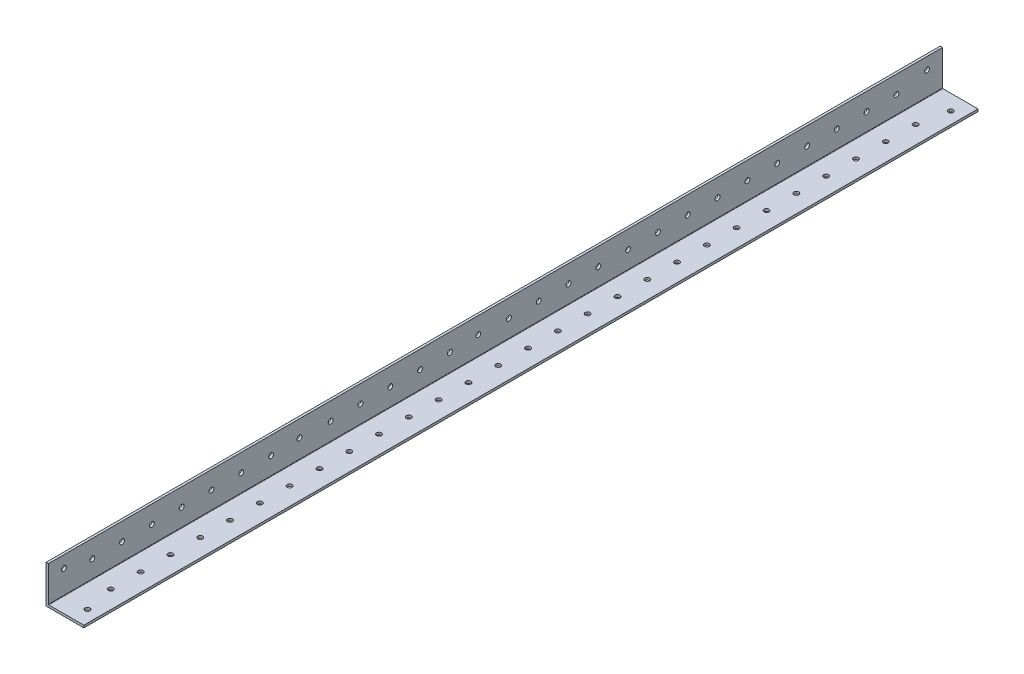
SolidWorks part; units mm, degrees
ref_plane "Front Plane" through (0, 0, 0) normal (0, 0, 1) x (1, 0, 0)
ref_plane "Top Plane" through (0, 0, 0) normal (0, 1, 0) x (1, 0, 0)
ref_plane "Right Plane" through (0, 0, 0) normal (1, 0, 0) x (0, 0, -1)
sketch "Sketch1" plane through (0, 0, 0) normal (0, 0, 1) x (1, 0, 0)
  line L0 (0, 25.4) -> (0, 0) construction
  line L1 (0, 0) -> (25.4, 0) construction
  line L2 (25.4, 0) -> (25.4, 1.5875) construction
  line L3 (25.4, 1.5875) -> (1.5875, 1.5875) construction
  line L4 (1.5875, 1.5875) -> (1.5875, 25.4) construction
  line L6 (1.5875, 25.4) -> (0, 25.4) construction
  arc A0 (1.5875, 1.8415) -> (1.8415, 1.5875) centre (1.8415, 1.8415) ccw construction
  point P4 (0, 0)
  dimension "Inside Corner Radius" = 0.254
  dimension "Outside Height" = 25.4
  dimension "Inside Height" = 23.8125
  dimension "Outside Width" = 25.4
  dimension "Inside Width" = 23.8125
  dimension "Wall Thickness" = 1.5875
  dimension "Shape" = 90
sketch "Sketch2" plane through (0, 0, 0) normal (1, 0, 0) x (0, 0, -1)
  line L0 (1219.2, 0) -> (-1219.2, 0) construction
  line L1 (-1219.2, 25.4) -> (-1219.2, 0) construction
  line L2 (1219.2, 25.4) -> (1219.2, 0) construction
  point P0 (-1189.99, 0)
  point P4 (0, 0)
  point P6 (1189.99, 0)
  dimension "D1" = 29.21
  dimension "D2" = 29.21
  dimension "D3" = 25.4
  dimension "Length" = 2438.4
sketch "Sketch3" plane through (0, 0, 0) normal (0, 0, 1) x (1, 0, 0)
  line L0 (1.5875, 25.4) -> (0, 25.4)
  line L1 (0, 25.4) -> (0, 0)
  line L2 (0, 0) -> (25.4, 0)
  line L3 (25.4, 0) -> (25.4, 1.5875)
  line L4 (25.4, 1.5875) -> (1.5875, 1.5875)
  line L5 (1.5875, 1.5875) -> (1.5875, 25.4)
extrude "Boss-Extrude1" add sketch "Sketch3" along normal mid plane 2438.4
fillet "Fillet1" radius 0.254 1 edges at (1.5875, 1.5875, 0)
sketch "Sketch4" plane through (0, 0, 0) normal (-1, 0, 0) x (0, 0, 1)
  line L0 (1219.2, 25.4) -> (1219.2, 0) construction
  line L1 (-1219.2, 0) -> (619.2, 0)
  line L2 (-1219.2, 0) -> (-1219.2, 74.9453)
  line L3 (-1219.2, 74.9453) -> (619.2, 74.9453)
  line L4 (619.2, 0) -> (619.2, 74.9453)
  dimension "D1" = 600
extrude "Cut-Extrude1" cut sketch "Sketch4" against normal blind 60
sketch "Sketch5" plane through (0, 1.5875, 0) normal (0, 1, 0) x (1, 0, 0)
  line L0 (17.4625, -1208.8241) -> (17.4625, -1189.2) construction
  line L1 (13.4937, -649.2) -> (13.4937, -629.5759) construction
  line L3 (1.5875, -1189.2) -> (25.4, -1189.2) construction
  line L4 (1.5875, -1219.2) -> (1.5875, -619.2) construction
  line L5 (25.4, -1219.2) -> (25.4, -619.2) construction
  line L6 (13.4937, -629.5759) -> (17.4625, -629.5759) construction
  line L7 (17.4625, -629.5759) -> (13.4937, -629.5759) construction
  circle A30 centre (17.4625, -629.5759) radius 1.65
  circle A31 centre (17.4625, -1208.8241) radius 1.65
  circle A32 centre (13.4938, -1189.2) radius 1.65
  circle A33 centre (13.4938, -1169.2) radius 1.65
  circle A34 centre (13.4938, -1149.2) radius 1.65
  circle A35 centre (13.4938, -1129.2) radius 1.65
  circle A36 centre (13.4938, -1109.2) radius 1.65
  circle A37 centre (13.4938, -1089.2) radius 1.65
  circle A38 centre (13.4938, -1069.2) radius 1.65
  circle A39 centre (13.4938, -1049.2) radius 1.65
  circle A40 centre (13.4938, -1029.2) radius 1.65
  circle A41 centre (13.4938, -1009.2) radius 1.65
  circle A42 centre (13.4938, -989.2) radius 1.65
  circle A43 centre (13.4938, -969.2) radius 1.65
  circle A44 centre (13.4938, -949.2) radius 1.65
  circle A45 centre (13.4938, -929.2) radius 1.65
  circle A46 centre (13.4938, -909.2) radius 1.65
  circle A47 centre (13.4938, -889.2) radius 1.65
  circle A48 centre (13.4938, -869.2) radius 1.65
  circle A49 centre (13.4938, -849.2) radius 1.65
  circle A50 centre (13.4938, -829.2) radius 1.65
  circle A51 centre (13.4938, -809.2) radius 1.65
  circle A52 centre (13.4938, -789.2) radius 1.65
  circle A53 centre (13.4938, -769.2) radius 1.65
  circle A54 centre (13.4938, -749.2) radius 1.65
  circle A55 centre (13.4938, -729.2) radius 1.65
  circle A56 centre (13.4938, -709.2) radius 1.65
  circle A57 centre (13.4938, -689.2) radius 1.65
  circle A58 centre (13.4938, -669.2) radius 1.65
  circle A59 centre (13.4937, -649.2) radius 1.65
  dimension "D1" = 3.3
  dimension "D2" = 3.3
  dimension "D3" = 28
  dimension "D4" = 20
extrude "Cut-Extrude2" cut sketch "Sketch5" against normal blind 10
sketch "Sketch9" plane through (1.5875, 0, 0) normal (1, 0, 0) x (0, 0, -1)
  line L0 (-1205.7062, 212.5245) -> (-1205.7062, 4.3115) construction
  line L1 (-1206.4453, 212.5245) -> (-1204.9672, 212.5245) construction
  line L2 (-1203.8241, 4.3115) -> (-1213.8241, 4.3115) construction
  line L3 (-1207.4063, -6.3505) -> (-1204.0063, -6.3505) construction
  line L4 (-634.3937, -3.175) -> (-630.9937, -3.175) construction
  line L5 (-634.3937, 0) -> (-634.3937, -6.35) construction
  line L6 (-630.9937, -6.35) -> (-630.9937, 0) construction
  line L7 (-1219.2, 1.5875) -> (-619.2, 1.5875) construction
  line L8 (-1189.7652, 25.4) -> (-1189.7652, 1.5875) construction
  line L9 (-1219.2, 25.4) -> (-619.2, 25.4) construction
  line L10 (-650.1411, 189.6802) -> (-650.1411, 177.774) construction
  line L11 (-1189.7652, 189.6802) -> (-1189.7652, 177.774) construction
  line L12 (-1219.2, 177.774) -> (-619.2, 177.774) construction
  line L16 (-629.5759, 17.4625) -> (-629.5759, 3.8186) construction
  line L17 (-623.0735, 3.8186) -> (-633.4875, 3.8186) construction
  line L18 (-650.1411, 13.4937) -> (-629.5759, 13.4937) construction
  circle A0 centre (-629.5759, 17.4625) radius 1.65
  circle A3 centre (-1208.8241, 17.4625) radius 1.65
  circle A16 centre (-1050.7062, 14.2875) radius 1.65
  circle A32 centre (-930.7062, 14.2875) radius 1.65
  circle A33 centre (-1189.7652, 13.4937) radius 1.65
  circle A34 centre (-1169.7652, 13.4937) radius 1.65
  circle A35 centre (-1149.7652, 13.4937) radius 1.65
  circle A36 centre (-1129.7652, 13.4937) radius 1.65
  circle A37 centre (-1109.7652, 13.4937) radius 1.65
  circle A38 centre (-1089.7652, 13.4937) radius 1.65
  circle A39 centre (-1069.7652, 13.4937) radius 1.65
  circle A40 centre (-1029.7652, 13.4937) radius 1.65
  circle A41 centre (-1009.7652, 13.4937) radius 1.65
  circle A42 centre (-989.7652, 13.4937) radius 1.65
  circle A43 centre (-969.7652, 13.4937) radius 1.65
  circle A44 centre (-949.7652, 13.4937) radius 1.65
  circle A73 centre (-650.1411, 13.4937) radius 1.65
  circle A75 centre (-670.1411, 13.4937) radius 1.65
  circle A76 centre (-690.1411, 13.4937) radius 1.65
  circle A77 centre (-710.1411, 13.4937) radius 1.65
  circle A78 centre (-730.1411, 13.4937) radius 1.65
  circle A79 centre (-750.1411, 13.4937) radius 1.65
  circle A80 centre (-770.1411, 13.4937) radius 1.65
  circle A81 centre (-790.1411, 13.4937) radius 1.65
  circle A94 centre (-810.1411, 13.4937) radius 1.65
  circle A95 centre (-830.1411, 13.4937) radius 1.65
  circle A96 centre (-850.1411, 13.4937) radius 1.65
  circle A97 centre (-870.1411, 13.4937) radius 1.65
  circle A98 centre (-890.1411, 13.4937) radius 1.65
  circle A99 centre (-910.1411, 13.4937) radius 1.65
  point P60 (-690.1411, 15.1313)
  point P64 (0, 0)
  point P89 (-910.1411, 13.4937)
  point P90 (-910.1411, 13.4937)
  dimension "D1" = 3.3
  dimension "D3" = 3.3
  dimension "D4" = 275
  dimension "D7" = 7
  dimension "D2" = 155
  dimension "D5" = 12.7
  dimension "D6" = 3.3
  dimension "D10" = 14
  dimension "D11" = 20
  dimension "D12" = 20
  dimension "D13" = 20
  dimension "D14" = 3.3
  dimension "D8" = 40
  dimension "D9" = 5
extrude "Cut-Extrude6" cut sketch "Sketch9" against normal blind 60
equation "\"D1@Boss-Extrude1\"=\"Length@Sketch2\""
equation "\"D1@Sketch2\" = \"Outside Width@Sketch1\" * 1.15"
equation "\"D2@Sketch2\"=\"D1@Sketch2\""
equation "\"D1@Fillet1\"=\"Inside Corner Radius@Sketch1\""
equation "\"D3@Sketch2\"=\"Outside Height@Sketch1\""
